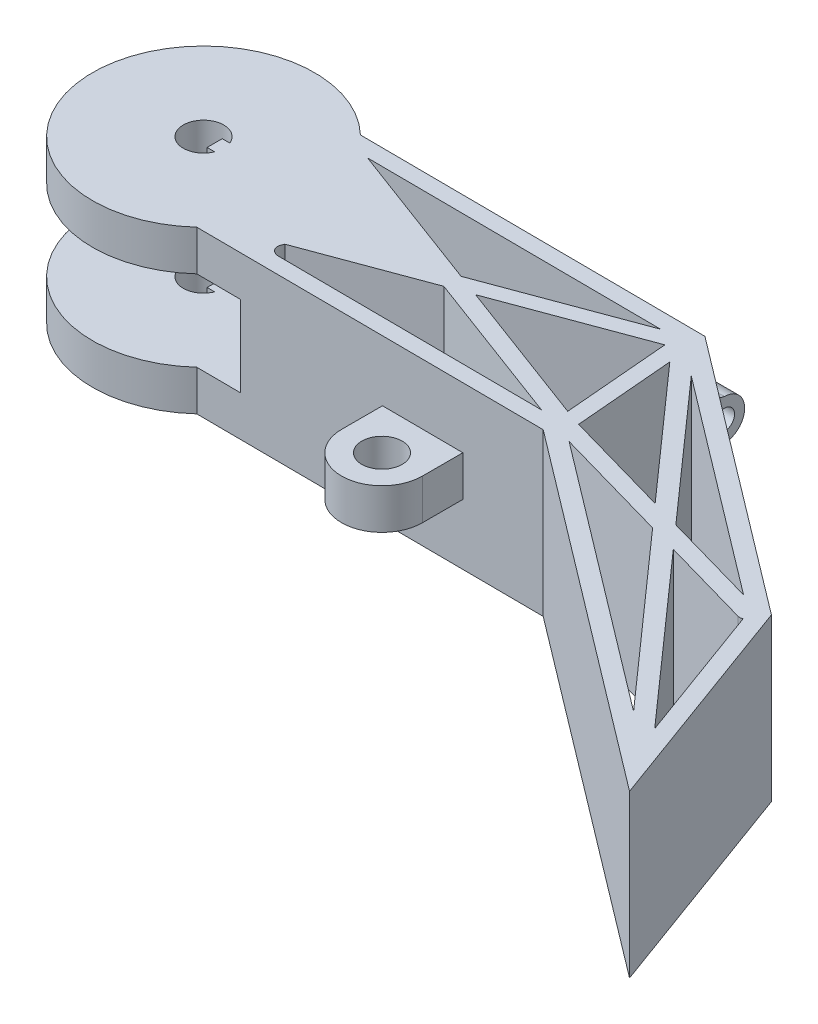
SolidWorks part; units mm, degrees
ref_plane "Front Plane" through (0, 0, 0) normal (0, 0, 1) x (1, 0, 0)
ref_plane "Top Plane" through (0, 0, 0) normal (0, 1, 0) x (1, 0, 0)
ref_plane "Right Plane" through (0, 0, 0) normal (1, 0, 0) x (0, 0, -1)
sketch "Sketch2" plane through (0, 0, 0) normal (0, 1, 0) x (1, 0, 0)
  line L0 (-86.363, -5.4396) -> (-1.4058, -5.4396) construction
  line L1 (-2.3879, -18.8413) -> (53.579, -61.2476)
  line L2 (53.579, -61.2476) -> (40.7275, -26.11)
  line L3 (-56.8308, 6.8962) -> (-2.3879, 6.5587)
  line L4 (40.7275, -26.11) -> (-2.3879, 6.5587)
  line L5 (-65.9872, -6.8458) -> (-67.1778, -6.8458)
  line L6 (-57.1449, -18.5018) -> (-2.3879, -18.8413)
  line L7 (-67.1778, -6.8458) -> (-67.1778, -4.4645)
  line L8 (-67.1778, -4.4645) -> (-65.9872, -4.4645)
  arc A0 (-57.1449, -18.5018) -> (-56.8308, 6.8962) centre (-68.9305, -5.6551) cw
  arc A1 (-65.9872, -4.4645) -> (-65.9872, -6.8458) centre (-68.9305, -5.6551) ccw
  point P15 (-67.1778, -5.6551)
  dimension "D4" = 1.1906
  dimension "D1" = 6.35
  dimension "D2" = 2.3813
  dimension "D3" = 25.4
extrude "Boss-Extrude4" add sketch "Sketch2" along normal blind 12.7
sketch "Sketch4" plane through (0, 12.7, 0) normal (0, 1, 0) x (1, 0, 0)
  circle A0 centre (-68.9305, -5.6551) radius 17.6534
extrude "Cut-Extrude1" cut sketch "Sketch4" against normal blind 6.35
sketch "Triangleout" plane through (0, 6.35, 0) normal (0, 1, 0) x (1, 0, 0)
  line L0 (-58.1063, -19.5103) -> (-49.8091, -19.5103)
  line L1 (-49.8091, -19.5103) -> (-52.889, -13.0249)
  line L2 (-52.889, -13.0249) -> (-58.1063, -19.5103)
  arc A0 (-56.8245, -18.5038) -> (-56.5145, 6.8942) centre (-68.9305, -5.6551) ccw construction
extrude "Cut-Extrude2" cut sketch "Triangleout" along normal blind 6.35
mirror "Mirror3" about plane through (-68.9305, 12.7, 5.6551) normal (0, -1, 0) of "Cut-Extrude2", "Cut-Extrude1", "Boss-Extrude4"
sketch "Sketch5" plane through (0, 25.4, 0) normal (0, 1, 0) x (1, 0, 0)
  line L0 (-1.5273, -16.3066) -> (-3.2484, 4.024) construction
  line L1 (48.2252, -54.0043) -> (-3.2484, 4.024)
  line L2 (47.1532, -43.6788) -> (-2.3879, -6.1413) construction
  line L3 (-57.1291, -15.9619) -> (-3.2484, 4.024)
  line L4 (53.579, -61.2476) -> (40.7275, -26.11) construction
  line L5 (-56.9899, -5.971) -> (-2.3879, -6.1413) construction
  line L6 (-57.1469, -18.67) -> (-56.8329, 6.7281) construction
  line L7 (-56.8466, 4.3563) -> (-1.5273, -16.3066)
  line L8 (-1.5273, -16.3066) -> (38.5985, -27.6836)
  line L10 (-56.6874, -17.1526) -> (-3.6217, 2.531)
  line L11 (47.2751, -54.847) -> (-3.6217, 2.531)
  line L12 (-57.2909, 3.1665) -> (-1.9234, -17.5144)
  line L13 (-1.9234, -17.5144) -> (38.252, -28.9054)
  line L14 (-57.5708, -14.7712) -> (-2.8752, 5.517)
  line L15 (49.1753, -53.1615) -> (-2.8752, 5.517)
  line L16 (-56.4022, 5.546) -> (-1.1312, -15.0988)
  line L17 (-1.1312, -15.0988) -> (38.9449, -26.4618)
  line L18 (-1.5273, -16.3066) -> (-3.2484, 4.024)
  line L19 (-0.2618, -16.1995) -> (-1.983, 4.1311)
  line L20 (-2.7928, -16.4137) -> (-4.5139, 3.9169)
  line L28 (-3.2484, 4.024) -> (-56.8466, 4.3563)
  line L29 (38.5985, -27.6836) -> (-3.2484, 4.024)
  line L30 (48.2252, -54.0043) -> (38.5985, -27.6836)
  line L31 (-1.5273, -16.3066) -> (48.2252, -54.0043)
  line L32 (-57.1291, -15.9619) -> (-1.5273, -16.3066)
  line L33 (-3.2484, 4.024) -> (-56.8466, 4.3563)
  line L34 (38.5985, -27.6836) -> (-3.2484, 4.024)
  line L35 (48.2252, -54.0043) -> (38.5985, -27.6836)
  line L36 (-1.5273, -16.3066) -> (48.2252, -54.0043)
  line L37 (-57.1291, -15.9619) -> (-1.5273, -16.3066)
  arc A0 (-56.6874, -17.1526) -> (-57.5708, -14.7712) centre (-57.1291, -15.9619) cw
  arc A1 (47.2751, -54.847) -> (49.1753, -53.1615) centre (48.2252, -54.0043) ccw
  arc A2 (-57.2909, 3.1665) -> (-56.4022, 5.546) centre (-56.8466, 4.3563) cw
  arc A3 (38.252, -28.9054) -> (38.9449, -26.4618) centre (38.5985, -27.6836) ccw
  arc A4 (-0.2618, -16.1995) -> (-2.7928, -16.4137) centre (-1.5273, -16.3066) cw
  arc A5 (-1.983, 4.1311) -> (-4.5139, 3.9169) centre (-3.2484, 4.024) ccw
  arc A7 (-57.1469, -18.67) -> (-56.8329, 6.7281) centre (-69.6889, -5.814) ccw
  spline S0 degree 1 poles (-57.1291, -15.9619) (-56.8466, 4.3563) knots 0 0 1 1
  spline S1 degree 2 poles (-47.0814, -16.0242) (-48.6847, -15.466) (-47.9144, -13.8984) knots 0 0 0 1 1 1
  dimension "D1" = 2.54
  dimension "D2" = 1.27
  dimension "D3" = 1.27
  dimension "D4" = 1.27
  dimension "D5" = 1.27
extrude "Cut-Extrude5" cut sketch "Sketch5" against normal through all contours L10 L37 L12 | L14 L33 L16 | L16 L20 L10 | A3 L13 L15 L35 | L13 L36 L11 | L17 L34 L15 | L19 L17 L11 region at (36.7581, 25.4, 34.9291) region at (21.2892, 25.4, 30.7012) region at (4.8128, 25.4, 11.6946) region at (19.5715, 25.4, 15.6129) region at (-28.9199, 25.4, 13.075) region at (-11.1296, 25.4, 5.9841) region at (-29.8963, 25.4, -1.3164)
sketch3d "3DSketch1"
  point P0 (-32.4816, 11.0258, -6.7453)
sketch3d "3DSketch2"
  point P0 (-24.5304, 25.4, -6.696)
sketch3d "3DSketch3"
  point P0 (-56.1674, 15.0984, -6.8921)
ref_plane "Plane3" through (-5.3674, 0, 0) normal (-1, 0, 0) x (0, 0, 1)
sketch "Sketch9" plane through (-5.3674, 0, 0) normal (-1, 0, 0) x (0, 0, 1)
  line L0 (-9.4342, 9.525) -> (-7.136, 8.9915) construction
  line L1 (-9.4342, 15.875) -> (-7.0942, 16.229) construction
  line L3 (-6.2815, 20.0314) -> (-6.2815, 5.8652) construction
  line L4 (-7.0942, 16.229) -> (-6.2815, 20.0314) construction
  line L6 (-7.136, 8.9915) -> (-6.2815, 5.8652) construction
  line L7 (-6.2815, 20.0314) -> (-6.2815, 5.8652)
  arc A0 (-9.4342, 15.875) -> (-9.4342, 9.525) centre (-9.4342, 12.7) ccw
  circle A1 centre (-9.4342, 12.7) radius 1.5875
  spline S0 degree 2 poles (-9.4342, 15.875) (-7.0942, 16.229) (-6.2815, 20.0314) knots 0 0 0 1 1 1
  spline S1 degree 2 poles (-9.4342, 9.525) (-7.136, 8.9915) (-6.2815, 5.8652) knots 0 0 0 1 1 1
  dimension "D2" = 3.175
  dimension "D3" = 3.175
extrude "Boss-Extrude6" add sketch "Sketch9" along normal blind 3.175 and the other way blind 3.175 separate body
sketch3d "3DSketch4"
  point P0 (0, 0, 0)
ref_plane "Plane4" through (0, 12.7, 0) normal (0, -1, 0) x (1, 0, 0)
sketch "Sketch10" plane through (0, 12.7, 0) normal (0, -1, 0) x (1, 0, 0)
  line L0 (-27.7879, 18.6838) -> (-15.0879, 18.7626)
  line L1 (-57.1449, 18.5018) -> (-2.3879, 18.8413) construction
  line L2 (-15.0879, 18.7626) -> (-15.0879, 25.1126)
  line L3 (-27.7879, 25.1126) -> (-27.7879, 18.6838)
  arc A0 (-27.7879, 25.1126) -> (-15.0879, 25.1126) centre (-21.4379, 25.1126) cw
  circle A1 centre (-21.4379, 25.1126) radius 3.175
  dimension "D1" = 6.35
  dimension "D2" = 6.35
  dimension "D3" = 6.35
  dimension "D4" = 19.05
extrude "Boss-Extrude7" add sketch "Sketch10" along normal blind 3.175 and the other way blind 3.175
sketch3d "3DSketch5"
  point P0 (-51.9133, 18.2273, 9.444)
ref_plane "Plane5" through (-87.4733, 0, 0) normal (-1, 0, 0) x (0, 0, 1)
